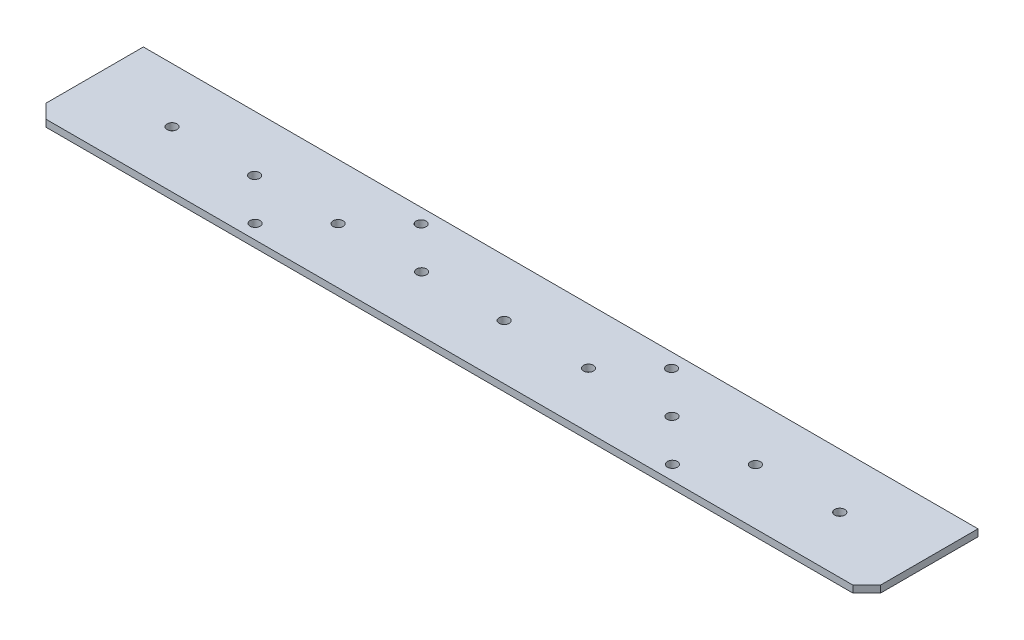
SolidWorks part; units mm, degrees
ref_plane "Front Plane" through (0, 0, 0) normal (0, 0, 1) x (1, 0, 0)
ref_plane "Top Plane" through (0, 0, 0) normal (0, 1, 0) x (1, 0, 0)
ref_plane "Right Plane" through (0, 0, 0) normal (1, 0, 0) x (0, 0, -1)
sketch "Sketch2" plane through (0, 0, 0) normal (0, 1, 0) x (1, 0, 0)
  line L0 (0, 0) -> (0, 50.8)
  line L1 (0, 50.8) -> (381, 50.8)
  line L2 (381, 50.8) -> (381, 0)
  line L3 (381, 0) -> (0, 0)
  dimension "D1" = 50.8
  dimension "D2" = 381
extrude "Boss-Extrude1" add sketch "Sketch2" along normal blind 3.175
sketch "Sketch3" plane through (0, 3.175, 0) normal (0, 1, 0) x (1, 0, 0)
  line L0 (190.5, 0) -> (190.5, 50.8) construction
  line L1 (0, 0) -> (381, 0) construction
  line L2 (381, 50.8) -> (0, 50.8) construction
  line L3 (38.1, 25.7969) -> (190.5, 25.0031) construction
  line L4 (342.9, 25.7969) -> (190.5, 25.0031) construction
  line L5 (0, 6.35) -> (6.35, 0)
  line L6 (6.35, 0) -> (0, 0)
  line L7 (0, 0) -> (0, 6.35)
  line L8 (374.65, 0) -> (381, 0)
  line L9 (381, 6.35) -> (374.65, 0)
  line L10 (381, 0) -> (381, 6.35)
  line L11 (247.65, 44.2526) -> (285.75, 6.5474) construction
  circle A0 centre (190.5, 25.0031) radius 2.286
  circle A1 centre (38.1, 25.7969) radius 2.286
  circle A2 centre (114.3, 25.4) radius 2.286
  circle A3 centre (76.2, 25.4) radius 2.286
  circle A4 centre (152.4, 25.4) radius 2.286
  circle A5 centre (228.6, 25.4) radius 2.286
  circle A6 centre (304.8, 25.4) radius 2.286
  circle A7 centre (266.7, 25.4) radius 2.286
  circle A8 centre (342.9, 25.7969) radius 2.286
  circle A9 centre (247.65, 44.2526) radius 2.286
  circle A10 centre (285.75, 6.5474) radius 2.286
  circle A11 centre (95.25, 6.5474) radius 2.286
  circle A12 centre (133.35, 44.2526) radius 2.286
  point P37 (266.7, 25.4)
  dimension "D1" = 4.572
  dimension "D2" = 0.7937
  dimension "D6" = 25.4
  dimension "D3" = 152.4
  dimension "D4" = 38.1
  dimension "D5" = 38.1
  dimension "D7" = 6.35
  dimension "D8" = 6.35
  dimension "D9" = 45
  dimension "D10" = 19.05
extrude "Cut-Extrude1" cut sketch "Sketch3" against normal up to next
